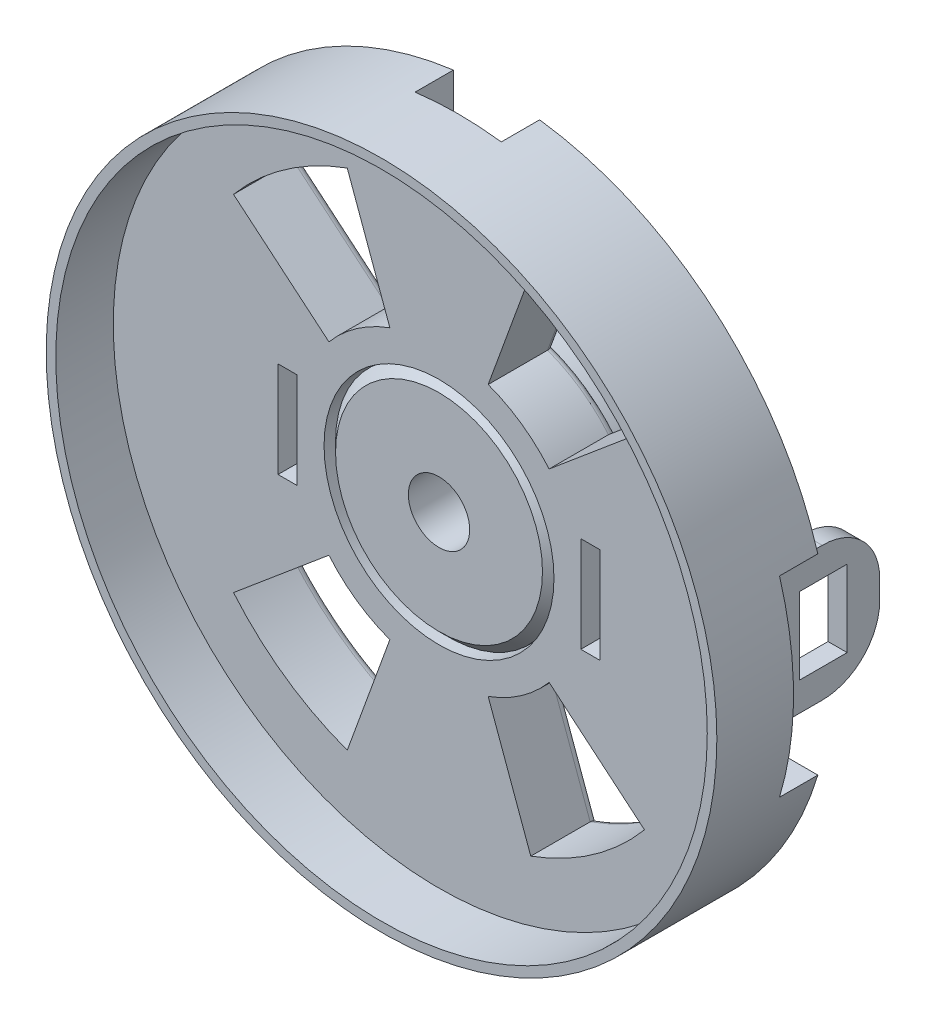
SolidWorks part; units mm, degrees
ref_plane "Front Plane" through (0, 0, 0) normal (0, 0, 1) x (1, 0, 0)
ref_plane "Top Plane" through (0, 0, 0) normal (0, 1, 0) x (1, 0, 0)
ref_plane "Right Plane" through (0, 0, 0) normal (1, 0, 0) x (0, 0, -1)
sketch "Sketch1" plane through (0, 0, 0) normal (0, 0, 1) x (1, 0, 0)
  circle A0 centre (0, 0) radius 17.5
extrude "Boss-Extrude1" add sketch "Sketch1" along normal blind 6
sketch "Sketch2" plane through (0, 0, 0) normal (0, 0, -1) x (-1, 0, 0)
  line L0 (2.5652, 7.0477) -> (4.7883, 13.1557)
  line L1 (5.7453, 4.8209) -> (10.7246, 8.999)
  line L3 (-5.7453, 4.8209) -> (-10.7246, 8.999)
  line L4 (-2.5652, 7.0477) -> (-4.7883, 13.1557)
  line L5 (-5.7453, -4.8209) -> (-10.7246, -8.999)
  line L6 (-2.5652, -7.0477) -> (-4.7883, -13.1557)
  line L7 (2.5652, -7.0477) -> (4.7883, -13.1557)
  line L8 (5.7453, -4.8209) -> (10.7246, -8.999)
  arc A1 (-10.7246, -8.999) -> (-4.7883, -13.1557) centre (0, 0) ccw
  arc A2 (2.5652, -7.0477) -> (5.7453, -4.8209) centre (0, 0) ccw
  arc A3 (5.7453, 4.8209) -> (2.5652, 7.0477) centre (0, 0) ccw
  arc A4 (-2.5652, 7.0477) -> (-5.7453, 4.8209) centre (0, 0) ccw
  arc A5 (-5.7453, -4.8209) -> (-2.5652, -7.0477) centre (0, 0) ccw
  arc A6 (-4.7883, 13.1557) -> (-10.7246, 8.999) centre (0, 0) ccw
  arc A7 (10.7246, 8.999) -> (4.7883, 13.1557) centre (0, 0) ccw
  arc A8 (4.7883, -13.1557) -> (10.7246, -8.999) centre (0, 0) ccw
  dimension "D1" = 7.5
  dimension "D3" = 14
  dimension "D2" = 30
extrude "Cut-Extrude1" cut sketch "Sketch2" against normal blind 10
sketch "Sketch4" plane through (0, 0, 0) normal (0, 0, -1) x (-1, 0, 0)
  line L4 (-3.4872, 13.6237) -> (-2.4078, 10.658)
  line L5 (-1.4681, 10) -> (1.4681, 10)
  line L6 (-10.7246, 8.999) -> (-5.7453, 4.8209) construction
  line L8 (3.4872, 13.6237) -> (2.4078, 10.658)
  line L9 (-2.5652, 7.0477) -> (-4.7883, 13.1557) construction
  line L10 (-3.4872, -13.6237) -> (-2.4078, -10.658)
  line L11 (-1.4681, -10) -> (1.4681, -10)
  line L12 (3.4872, -13.6237) -> (2.4078, -10.658)
  line L13 (-10.7246, 8.999) -> (-5.7453, 4.8209)
  line L14 (-2.5652, 7.0477) -> (-4.7883, 13.1557)
  line L15 (2.5652, -7.0477) -> (4.7883, -13.1557) construction
  line L16 (10.7246, -8.999) -> (5.7453, -4.8209) construction
  line L17 (4.7883, 13.1557) -> (2.5652, 7.0477) construction
  line L18 (5.7453, 4.8209) -> (10.7246, 8.999) construction
  line L19 (2.5652, -7.0477) -> (4.7883, -13.1557)
  line L20 (10.7246, -8.999) -> (5.7453, -4.8209)
  line L21 (4.7883, 13.1557) -> (2.5652, 7.0477)
  line L22 (5.7453, 4.8209) -> (10.7246, 8.999)
  line L23 (-4.7883, -13.1557) -> (-2.5652, -7.0477) construction
  line L24 (-5.7453, -4.8209) -> (-10.7246, -8.999) construction
  line L25 (-4.7883, -13.1557) -> (-2.5652, -7.0477)
  line L26 (-5.7453, -4.8209) -> (-10.7246, -8.999)
  line L27 (-10.4264, 7.3007) -> (-11.4388, 8.0096)
  line L28 (-10, 6.4815) -> (-10, -6.4815)
  line L30 (-10.4264, -7.3007) -> (-11.4388, -8.0096)
  line L31 (10.4264, -7.3007) -> (11.4388, -8.0096)
  line L32 (10.4264, 7.3007) -> (11.4388, 8.0096)
  line L33 (10, 6.4815) -> (10, -6.4815)
  arc A0 (-4.7432, 14.2303) -> (-11.6413, 9.4593) centre (0, 0) ccw
  arc A1 (4.7432, -14.2303) -> (11.6413, -9.4593) centre (0, 0) ccw
  arc A2 (-2.5652, 7.0477) -> (-5.7453, 4.8209) centre (0, 0) ccw construction
  arc A3 (-4.7883, 13.1557) -> (-10.7246, 8.999) centre (0, 0) ccw construction
  arc A4 (-2.5652, 7.0477) -> (-5.7453, 4.8209) centre (0, 0) ccw
  arc A5 (-4.7883, 13.1557) -> (-10.7246, 8.999) centre (0, 0) ccw
  arc A6 (4.7883, -13.1557) -> (10.7246, -8.999) centre (0, 0) ccw construction
  arc A7 (2.5652, -7.0477) -> (5.7453, -4.8209) centre (0, 0) ccw construction
  arc A8 (5.7453, 4.8209) -> (2.5652, 7.0477) centre (0, 0) ccw construction
  arc A9 (10.7246, 8.999) -> (4.7883, 13.1557) centre (0, 0) ccw construction
  arc A10 (4.7883, -13.1557) -> (10.7246, -8.999) centre (0, 0) ccw
  arc A11 (2.5652, -7.0477) -> (5.7453, -4.8209) centre (0, 0) ccw
  arc A12 (5.7453, 4.8209) -> (2.5652, 7.0477) centre (0, 0) ccw
  arc A13 (10.7246, 8.999) -> (4.7883, 13.1557) centre (0, 0) ccw
  arc A14 (-10.7246, -8.999) -> (-4.7883, -13.1557) centre (0, 0) ccw construction
  arc A15 (-5.7453, -4.8209) -> (-2.5652, -7.0477) centre (0, 0) ccw construction
  arc A16 (-10.7246, -8.999) -> (-4.7883, -13.1557) centre (0, 0) ccw
  arc A17 (-5.7453, -4.8209) -> (-2.5652, -7.0477) centre (0, 0) ccw
  arc A18 (-11.6413, -9.4593) -> (-4.7432, -14.2303) centre (0, 0) ccw
  arc A19 (11.6413, 9.4593) -> (4.7432, 14.2303) centre (0, 0) ccw
  arc A20 (-11.4388, 8.0096) -> (-11.6413, 9.4593) centre (-10.8653, 8.8287) cw
  arc A21 (-10, 6.4815) -> (-10.4264, 7.3007) centre (-11, 6.4815) ccw
  arc A22 (-10, -6.4815) -> (-10.4264, -7.3007) centre (-11, -6.4815) cw
  arc A23 (-11.4388, -8.0096) -> (-11.6413, -9.4593) centre (-10.8653, -8.8287) ccw
  arc A24 (-3.4872, -13.6237) -> (-4.7432, -14.2303) centre (-4.4269, -13.2816) cw
  arc A25 (-2.4078, -10.658) -> (-1.4681, -10) centre (-1.4681, -11) cw
  arc A26 (1.4681, -10) -> (2.4078, -10.658) centre (1.4681, -11) cw
  arc A27 (3.4872, -13.6237) -> (4.7432, -14.2303) centre (4.4269, -13.2816) ccw
  arc A28 (11.4388, -8.0096) -> (11.6413, -9.4593) centre (10.8653, -8.8287) cw
  arc A29 (10.4264, -7.3007) -> (10, -6.4815) centre (11, -6.4815) cw
  arc A30 (10.4264, 7.3007) -> (10, 6.4815) centre (11, 6.4815) ccw
  arc A31 (11.4388, 8.0096) -> (11.6413, 9.4593) centre (10.8653, 8.8287) ccw
  arc A32 (3.4872, 13.6237) -> (4.7432, 14.2303) centre (4.4269, 13.2816) cw
  arc A33 (2.4078, 10.658) -> (1.4681, 10) centre (1.4681, 11) cw
  arc A34 (-1.4681, 10) -> (-2.4078, 10.658) centre (-1.4681, 11) cw
  arc A35 (-3.4872, 13.6237) -> (-4.7432, 14.2303) centre (-4.4269, 13.2816) ccw
  dimension "D3" = 30
  dimension "D4" = 1
  dimension "D1" = 10
  dimension "D2" = 10
extrude "Boss-Extrude2" add sketch "Sketch4" along normal blind 0.5
fillet "Fillet2" radius 0.4 48 edges at (8.235, -6.91, -0.5) (8.0301, -11.4681, -0.5) (3.6767, -10.1017, -0.5) (4.3018, -6.1436, -0.5) (-3.6767, -10.1017, -0.5) (-8.0301, -11.4681, -0.5) (-8.235, -6.91, -0.5) (-4.3018, -6.1436, -0.5) (8.5325, 12.3368, -0.5) (3.992, 14.1821, -0.5) (2.9475, 12.1408, -0.5) (2.0417, 10.1808, -0.5) (0, 10, -0.5) (-2.0417, 10.1808, -0.5) (-2.9475, 12.1408, -0.5) (-3.992, 14.1821, -0.5) (-8.5325, 12.3368, -0.5) (-11.8556, 8.6904, -0.5) (-10.9326, 7.6551, -0.5) (-10.113, 6.9433, -0.5) (-10, 0, -0.5) (-10.113, -6.9433, -0.5) (-10.9326, -7.6551, -0.5) (-11.8556, -8.6904, -0.5) (-8.5325, -12.3368, -0.5) (-3.992, -14.1821, -0.5) (-2.9475, -12.1408, -0.5) (-2.0417, -10.1808, -0.5) (0, -10, -0.5) (2.0417, -10.1808, -0.5) (2.9475, -12.1408, -0.5) (3.992, -14.1821, -0.5) (8.5325, -12.3368, -0.5) (11.8556, -8.6904, -0.5) (10.9326, -7.6551, -0.5) (10.113, -6.9433, -0.5) (10, 0, -0.5) (10.113, 6.9433, -0.5) (10.9326, 7.6551, -0.5) (11.8556, 8.6904, -0.5) (8.235, 6.91, -0.5) (4.3018, 6.1436, -0.5) (3.6767, 10.1017, -0.5) (8.0301, 11.4681, -0.5) (-3.6767, 10.1017, -0.5) (-4.3018, 6.1436, -0.5) (-8.235, 6.91, -0.5) (-8.0301, 11.4681, -0.5)
sketch "Sketch5" plane through (0, 0, -0.5) normal (0, 0, -1) x (-1, 0, 0)
  circle A0 centre (0, 0) radius 6.5
extrude "Boss-Extrude3" add sketch "Sketch5" along normal blind 4.5
fillet "Fillet3" radius 0.5 1 edges at (-6.5, 0, -5)
sketch "Sketch6" plane through (0, 0, -5) normal (0, 0, -1) x (-1, 0, 0)
  circle A0 centre (0, 0) radius 6
extrude "Cut-Extrude2" cut sketch "Sketch6" against normal through all
chamfer "Chamfer1" distance 0.5 angle 45 1 edges at (-6, 0, 6)
sketch "Sketch7" plane through (0, 0, 6) normal (0, 0, 1) x (1, 0, 0)
  circle A0 centre (0, 0) radius 17
extrude "Cut-Extrude3" cut sketch "Sketch7" against normal blind 3
sketch "Sketch8" plane through (0, 0, -0.5) normal (0, 0, -1) x (-1, 0, 0)
  line L1 (7.4, 2.5) -> (8.4, 2.5)
  line L2 (7.4, 2.5) -> (7.4, -2.5)
  line L3 (7.4, -2.5) -> (8.4, -2.5)
  line L4 (8.4, 2.5) -> (8.4, -2.5)
  line L5 (-8.4, 2.5) -> (-7.4, 2.5)
  line L6 (-8.4, 2.5) -> (-8.4, -2.5)
  line L7 (-8.4, -2.5) -> (-7.4, -2.5)
  line L8 (-7.4, 2.5) -> (-7.4, -2.5)
  point P8 (7.4, 0)
  point P10 (-7.4, 0)
  dimension "D1" = 1
  dimension "D2" = 5
  dimension "D3" = 0
  dimension "D4" = 7.4
  dimension "D5" = 7.4
  dimension "D6" = 1
  dimension "D7" = 5
  dimension "D8" = 0
extrude "Cut-Extrude4" cut sketch "Sketch8" against normal through all and the other way through all
sketch "Sketch9" plane through (0, 0, 3) normal (0, 0, 1) x (1, 0, 0)
  circle A0 centre (0, 0) radius 5.9
extrude "Boss-Extrude4" add sketch "Sketch9" against normal blind 8 separate body
chamfer "Chamfer2" distance 0.5 angle 45 2 edges at (5.9, 0, 3) (5.9, 0, -5)
sketch "Sketch10" plane through (0, 0, -5) normal (0, 0, -1) x (-1, 0, 0)
  circle A0 centre (0, 0) radius 1.6
  dimension "D1" = 3.2
extrude "Cut-Extrude5" cut sketch "Sketch10" against normal through all
sketch "Sketch11" plane through (0, 0, 0) normal (0, 0, -1) x (-1, 0, 0)
  line L1 (-19.3808, 5) -> (-12.5, 5)
  line L2 (-19.3808, 5) -> (-19.3808, -5)
  line L3 (-19.3808, -5) -> (-12.5, -5)
  line L4 (-12.5, 5) -> (-12.5, -5)
  line L5 (12.5, 5) -> (12.5, -5)
  line L6 (19.3808, -5) -> (12.5, -5)
  line L7 (19.3808, 5) -> (19.3808, -5)
  line L8 (19.3808, 5) -> (12.5, 5)
  dimension "D1" = 12.5
  dimension "D2" = 5
  dimension "D3" = 10
extrude "Cut-Extrude6" cut sketch "Sketch11" against normal blind 2
sketch "Sketch12" plane through (0, 0, 0) normal (0, 0, -1) x (-1, 0, 0)
  line L1 (-2.25, 19.4199) -> (2.25, 19.4199)
  line L2 (-2.25, 19.4199) -> (-2.25, 14)
  line L3 (-2.25, 14) -> (2.25, 14)
  line L4 (2.25, 19.4199) -> (2.25, 14)
  line L5 (2.25, -19.4199) -> (2.25, -14)
  line L6 (-2.25, -14) -> (2.25, -14)
  line L7 (-2.25, -19.4199) -> (-2.25, -14)
  line L8 (-2.25, -19.4199) -> (2.25, -19.4199)
  dimension "D1" = 4.5
  dimension "D2" = 2.25
  dimension "D3" = 14
extrude "Cut-Extrude7" cut sketch "Sketch12" against normal blind 2
fillet "Fillet4" radius 1 4 edges at (12.5, -5, 1) (12.5, 5, 1) (-12.5, -5, 1) (-12.5, 5, 1)
fillet "Fillet5" radius 0.5 4 edges at (-2.25, -14, 1) (2.25, -14, 1) (-2.25, 14, 1) (2.25, 14, 1)
sketch "Sketch13" plane through (0, 0, 2) normal (0, 0, -1) x (-1, 0, 0)
  line L0 (-13.5, 5) -> (-16.7705, 5) construction
  line L1 (-15, 3.5) -> (-14, 3.5)
  line L2 (-15, 3.5) -> (-15, -3.5)
  line L3 (-15, -3.5) -> (-14, -3.5)
  line L4 (-14, 3.5) -> (-14, -3.5)
  line L5 (-16.7705, -5) -> (-13.5, -5) construction
  line L6 (-12.5, -4) -> (-12.5, 4) construction
  line L8 (14, 3.5) -> (14, -3.5)
  line L9 (15, -3.5) -> (14, -3.5)
  line L10 (15, 3.5) -> (15, -3.5)
  line L11 (15, 3.5) -> (14, 3.5)
  dimension "D1" = 1.5
  dimension "D2" = 1.5
  dimension "D3" = 1
  dimension "D4" = 1.5
extrude "Boss-Extrude5" add sketch "Sketch13" along normal blind 7
fillet "Fillet6" radius 3 4 edges at (14.5, -3.5, -5) (14.5, 3.5, -5) (-14.5, -3.5, -5) (-14.5, 3.5, -5)
sketch "Sketch14" plane through (15, 0, 0) normal (1, 0, 0) x (0, 0, -1)
  line L0 (2, 3.5) -> (-2, 3.5) construction
  line L1 (0.8, 2) -> (3.3, 2)
  line L2 (0.8, 2) -> (0.8, -2)
  line L3 (0.8, -2) -> (3.3, -2)
  line L4 (3.3, 2) -> (3.3, -2)
  line L5 (2, -3.5) -> (-2, -3.5) construction
  line L6 (-2, -5) -> (-2, 5) construction
  point P8 (2.05, -2)
  dimension "D1" = 2.5
  dimension "D2" = 1.5
  dimension "D3" = 1.5
  dimension "D4" = 2.8
extrude "Cut-Extrude8" cut sketch "Sketch14" against normal blind 3
ref_axis "Axis1" through (0, 0, -4.5) along (0, 0, 1)
pattern_circular "CirPattern1" count 2 over 360 about axis through (0, 0, -4.5) along (0, 0, 1) of "Cut-Extrude8"
